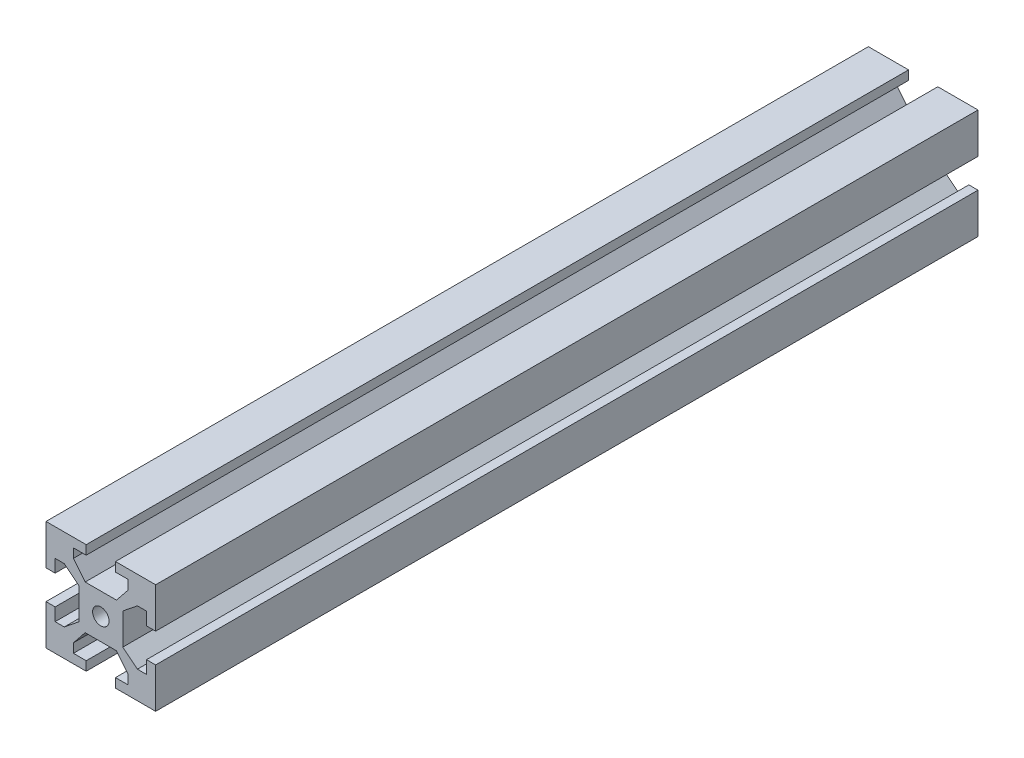
SolidWorks part; units mm, degrees
ref_plane "Front Plane" through (0, 0, 0) normal (0, 0, 1) x (1, 0, 0)
ref_plane "Top Plane" through (0, 0, 0) normal (0, 1, 0) x (1, 0, 0)
ref_plane "Right Plane" through (0, 0, 0) normal (1, 0, 0) x (0, 0, -1)
sketch "Sketch1" plane through (0, 0, 0) normal (0, 0, 1) x (1, 0, 0)
  line L1 (10, 10) -> (2.6667, 10)
  line L2 (10, 10) -> (10, 2.6667)
  line L3 (10, -10) -> (2.6667, -10)
  line L4 (-10, 10) -> (-10, 2.6667)
  line L6 (8.3333, -2.6667) -> (10, -2.6667)
  line L7 (10, 0) -> (4, 0) construction
  line L8 (10, -2.6667) -> (10, -10)
  line L9 (10, 2.6667) -> (10, 0) construction
  line L10 (10, 0) -> (10, -2.6667) construction
  line L11 (8.3333, -2.6667) -> (8.3333, -5)
  line L12 (8.3333, -5) -> (6.6667, -5)
  line L13 (6.6667, -5) -> (4, -2.8571)
  line L14 (4, -2.8571) -> (4, 2.8571)
  line L16 (5, -6.6667) -> (2.8571, -4)
  line L17 (8.3333, 2.6667) -> (10, 2.6667)
  line L18 (8.3333, 2.6667) -> (8.3333, 5)
  line L19 (8.3333, 5) -> (6.6667, 5)
  line L20 (6.6667, 5) -> (4, 2.8571)
  line L21 (-10, 0) -> (10, 0) construction
  line L22 (-2.8571, -4) -> (2.8571, -4)
  line L23 (-5, -6.6667) -> (-2.8571, -4)
  line L24 (-5, -8.3333) -> (-5, -6.6667)
  line L25 (-2.6667, -8.3333) -> (-5, -8.3333)
  line L26 (-2.6667, -8.3333) -> (-2.6667, -10)
  line L27 (2.6667, -8.3333) -> (2.6667, -10)
  line L28 (2.6667, -8.3333) -> (5, -8.3333)
  line L29 (5, -8.3333) -> (5, -6.6667)
  line L30 (-6.6667, -5) -> (-4, -2.8571)
  line L31 (-4, 2.8571) -> (-4, -2.8571)
  line L32 (-6.6667, 5) -> (-4, 2.8571)
  line L33 (-8.3333, 5) -> (-6.6667, 5)
  line L34 (-8.3333, 2.6667) -> (-8.3333, 5)
  line L35 (-8.3333, 2.6667) -> (-10, 2.6667)
  line L36 (-8.3333, -2.6667) -> (-10, -2.6667)
  line L37 (-8.3333, -2.6667) -> (-8.3333, -5)
  line L38 (-8.3333, -5) -> (-6.6667, -5)
  line L39 (-5, 6.6667) -> (-2.8571, 4)
  line L40 (2.8571, 4) -> (-2.8571, 4)
  line L41 (5, 6.6667) -> (2.8571, 4)
  line L42 (5, 8.3333) -> (5, 6.6667)
  line L43 (2.6667, 8.3333) -> (5, 8.3333)
  line L44 (2.6667, 8.3333) -> (2.6667, 10)
  line L45 (-2.6667, 8.3333) -> (-2.6667, 10)
  line L46 (-2.6667, 8.3333) -> (-5, 8.3333)
  line L47 (-5, 8.3333) -> (-5, 6.6667)
  line L48 (-2.6667, 10) -> (-10, 10)
  line L49 (2.6667, 10) -> (-2.6667, 10) construction
  line L50 (-10, -2.6667) -> (-10, -10)
  line L51 (-10, 2.6667) -> (-10, 0) construction
  line L52 (-10, 0) -> (-10, -2.6667) construction
  line L53 (-2.6667, -10) -> (-10, -10)
  line L54 (2.6667, -10) -> (-2.6667, -10) construction
  circle A0 centre (0, 0) radius 1.5
  point P6 (0, 0)
  point P54 (-4, 0)
  dimension "D7" = 3
  dimension "D2" = 20
  dimension "D1" = 5.3333
  dimension "D3" = 1.6667
  dimension "D4" = 6
  dimension "D5" = 2.8571
  dimension "D6" = 5
  dimension "D9" = 4
extrude "Boss-Extrude1" add sketch "Sketch1" along normal mid plane 150
ref_axis "Axis1" through (0, 0, -7.5) along (0, 0, 1)
equation "\"var1\"= 20"
equation "\"D2@Sketch1\"=\"var1\""
equation "\"D1@Sketch1\"=\"var1\"/3.75"
equation "\"D3@Sketch1\"=\"var1\"/12"
equation "\"D4@Sketch1\"=\"var1\"*0.3"
equation "\"D5@Sketch1\"=\"var1\"/7"
equation "\"D6@Sketch1\"=\"var1\"/4"
